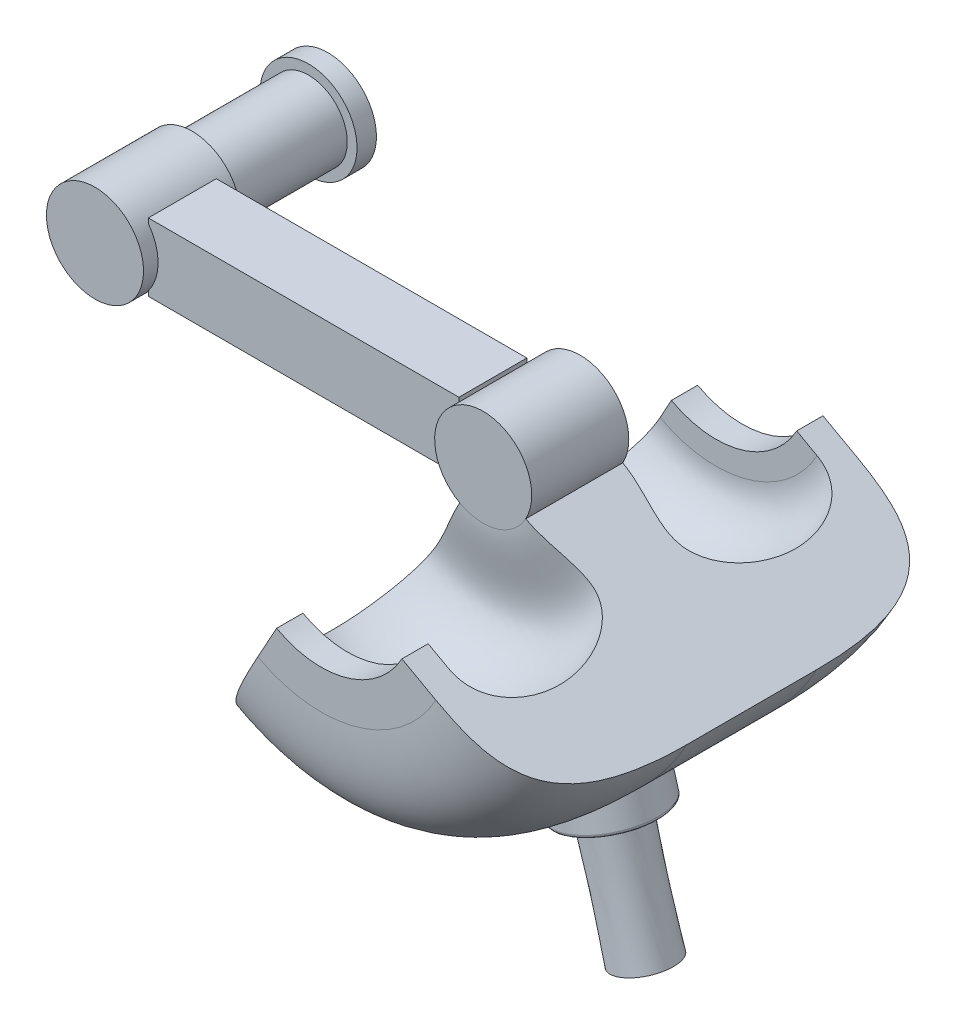
SolidWorks part; units mm, degrees
ref_plane "Front Plane" through (0, 0, 0) normal (0, 0, 1) x (1, 0, 0)
ref_plane "Top Plane" through (0, 0, 0) normal (0, 1, 0) x (1, 0, 0)
ref_plane "Right Plane" through (0, 0, 0) normal (1, 0, 0) x (0, 0, -1)
sketch "Sketch1" plane through (0, 0, 0) normal (0, 0, 1) x (1, 0, 0)
  line L0 (100, 0) -> (-100, 0)
  line L1 (-100, 0) -> (-84.615, -53.2945) construction
  line L2 (-84.615, -53.2945) -> (100, 0) construction
  line L3 (-84.615, -53.2945) -> (-100, 0) construction
  line L4 (-100, 0) -> (-148.4737, 167.9155) construction
  line L5 (-100, 0) -> (-115.2545, 52.8422)
  line L6 (-100, 0) -> (84.615, 53.2945) construction
  line L7 (84.615, 53.2945) -> (100, 0) construction
  line L8 (84.615, 53.2945) -> (100, 0) construction
  line L9 (100, 0) -> (139.1778, -135.7138) construction
  line L10 (100, 0) -> (115.2545, -52.8422)
  circle A0 centre (-100, 0) radius 25
  circle A1 centre (100, 0) radius 25
  point P4 (0, 0)
  dimension "D2" = 16.102
  dimension "D1" = 200
  dimension "D3" = 55
  dimension "D4" = 16.102
  dimension "D5" = 55
sketch "Sketch2" plane through (0, 0, 0) normal (0, 1, 0) x (1, 0, 0)
  line L0 (-100, -30.0778) -> (-100, 0) construction
  line L1 (-120, 0) -> (-111.4048, -6.7332)
  line L2 (-120, 0) -> (-100, 0)
  line L3 (-105, -30.0778) -> (-105, -15.0778)
  line L4 (-100, 0) -> (-100, -30.0778)
  line L5 (-100, -30.0778) -> (-105, -30.0778)
  line L6 (-125, 0) -> (-75, 0) construction
  line L9 (-125, -5) -> (-125, -7.9927) construction
  line L10 (-125, -5) -> (-125, -15.0778)
  line L11 (-115, -15.0778) -> (-125, -15.0778)
  line L12 (-125, -5) -> (-125, 0)
  line L13 (-125, 0) -> (-120, 0)
  line L14 (-113.6173, -5) -> (-113.6173, -15.0778)
  line L15 (-113.6173, -15.0778) -> (-115, -15.0778)
  line L16 (-113.6173, -15.0778) -> (-105, -15.0778)
  spline S0 degree 3 poles (-111.4048, -6.7332) (-109.6654, -8.0958) (-107.132, -10.6266) (-105, -13.4894) (-105, -15.0778) knots 0 0 0 0 0.616179 1 1 1 1
  dimension "D1" = 5
  dimension "D2" = 20
  dimension "D3" = 10.9185
  dimension "D4" = 15
  dimension "D5" = 5
  dimension "D6" = 5
  dimension "D7" = 5
  dimension "D8" = 10
  dimension "D9" = 15
  dimension "D10" = 15.0778
sketch "Sketch3" plane through (0, 0, 0) normal (0, 1, 0) x (1, 0, 0)
  line L5 (-125, -7.5389) -> (-80.1507, -7.5389) construction
  line L8 (-120, 0) -> (-100, 0) construction
  line L9 (-125, -32.5389) -> (-125, 17.4611)
  line L10 (-100, 0) -> (-100, 17.4611)
  line L11 (-100, 17.4611) -> (-125, 17.4611)
  line L12 (-100, 0) -> (-100, -15.0778)
  line L13 (-100, 0) -> (-100, -30.0778) construction
  line L14 (-100, -15.0778) -> (-100, -32.5389)
  line L15 (-100, -32.5389) -> (-125, -32.5389)
  point P10 (-100, -7.5389)
  dimension "D1" = 7.5389
  dimension "D2" = 25
revolve "Revolve2" add sketch "Sketch3" angle 360 about L4
sketch "Sketch4" plane through (0, 0, 0) normal (0, 0, 1) x (1, 0, 0)
  circle A0 centre (100, 0) radius 25
ref_plane "Plane1" through (80, 0, 0) normal (1, 0, 0) x (0, 0, -1)
ref_plane "Plane2" through (-80, 0, 0) normal (1, 0, 0) x (0, 0, -1)
sketch "Sketch5" plane through (80, 0, 0) normal (1, 0, 0) x (0, 0, -1)
  line L11 (9.9611, -17.5) -> (-25.0389, -17.5)
  line L12 (9.9611, -17.5) -> (9.9611, 17.5)
  line L13 (9.9611, 17.5) -> (-25.0389, 17.5)
  line L14 (-25.0389, -17.5) -> (-25.0389, 17.5)
  point P12 (-7.5389, 0)
  dimension "D1" = 35
  dimension "D2" = 35
sketch "Sketch6" plane through (-80, 0, 0) normal (1, 0, 0) x (0, 0, -1)
  line L12 (9.9611, -17.5) -> (-25.0389, -17.5)
  line L13 (9.9611, -17.5) -> (9.9611, 17.5)
  line L14 (9.9611, 17.5) -> (-25.0389, 17.5)
  line L15 (-25.0389, -17.5) -> (-25.0389, 17.5)
  point P6 (-7.5389, 0)
  dimension "D1" = 35
  dimension "D2" = 35
sketch "Sketch7" plane through (0, 0, 0) normal (1, 0, 0) x (0, 0, -1)
  line L0 (-7.5389, 45) -> (-7.5389, -15)
  point P3 (-7.5389, 15)
ref_plane "Plane3" through (0, 0, 7.5389) normal (0, 0, 1) x (1, 0, 0)
loft "Loft2" add profiles "Sketch6", "Sketch5" connector at (-80, -17.5, -9.9611) connector at (80, -17.5, -9.9611)
sketch "Sketch10" plane through (0, 0, 7.5389) normal (0, 0, 1) x (1, 0, 0)
  circle A0 centre (100, 0) radius 25
extrude "Boss-Extrude2" add sketch "Sketch10" along normal mid plane 50
sketch "Sketch11" plane through (0, 0, 7.5389) normal (0, 0, 1) x (1, 0, 0)
  line L0 (100, 0) -> (115.2545, -52.8422) construction
ref_plane "Plane4" through (7.6925, -26.6473, 0) normal (0.2774, -0.9608, 0) x (-0.9608, -0.2774, 0)
ref_plane "Plane5" through (92.3075, 26.6473, 0) normal (0.9608, 0.2774, 0) x (0, 0, -1)
sketch "Sketch12" plane through (92.3075, 26.6473, 0) normal (0.9608, 0.2774, 0) x (0, 0, -1)
  line L0 (-32.5389, -75.009) -> (17.4611, -75.009) construction
  line L1 (-32.5389, -2.7354) -> (-32.5389, -52.7354) construction
  line L2 (17.4611, -52.7354) -> (17.4611, -2.7354) construction
  line L3 (-7.5389, -84.4009) -> (-7.5389, -65.617)
  line L4 (-22.5389, -65.617) -> (-47.5389, -65.617)
  line L5 (-47.5389, -65.617) -> (-47.5389, -78.1293)
  line L6 (-7.5389, -65.617) -> (-7.5389, -132.7956) construction
  line L7 (-22.5389, -65.617) -> (-22.5389, -52.7354)
  line L8 (-32.5389, -52.7354) -> (17.4611, -52.7354) construction
  line L9 (-127.5389, -120.3474) -> (-132.5389, -120.3474)
  line L10 (-132.5389, -120.3474) -> (-132.5389, -150.3474)
  line L11 (-132.5389, -150.3474) -> (-112.5389, -150.3474)
  line L12 (-112.5389, -150.3474) -> (-112.5389, -128.4544)
  line L13 (-47.5389, -108.1293) -> (32.4611, -108.1293)
  line L14 (-90.9173, -108.1293) -> (-47.5389, -108.1293)
  line L15 (117.4611, -120.3474) -> (117.4611, -150.3474)
  line L16 (117.4611, -150.3474) -> (97.4611, -150.3474)
  line L17 (97.4611, -150.3474) -> (97.4611, -128.4544)
  line L18 (75.8395, -108.1293) -> (32.4611, -108.1293)
  line L19 (32.4611, -65.617) -> (32.4611, -78.1293)
  line L20 (7.4611, -65.617) -> (32.4611, -65.617)
  line L21 (7.4611, -65.617) -> (7.4611, -52.7354)
  line L22 (112.4611, -120.3474) -> (117.4611, -120.3474)
  line L23 (-112.5389, -139.4009) -> (-7.5389, -139.4009) construction
  line L24 (-32.5389, -27.7354) -> (-61.8307, -27.7354) construction
  spline S0 degree 3 poles (-47.5389, -78.1293) (-56.791, -78.1293) (-92.4711, -91.2818) (-119.9145, -99.872) (-127.5389, -120.3474) knots 0 0 0 0 0.409199 1 1 1 1
  spline S1 degree 2 poles (-112.5389, -128.4544) (-109.5542, -110.7568) (-90.9173, -108.1293) knots 0 0 0 1 1 1
  spline S2 degree 2 poles (97.4611, -128.4544) (94.4764, -110.7568) (75.8395, -108.1293) knots 0 0 0 1 1 1
  spline S3 degree 3 poles (32.4611, -78.1293) (41.7132, -78.1293) (77.3933, -91.2818) (104.8367, -99.872) (112.4611, -120.3474) knots 0 0 0 0 0.409199 1 1 1 1
  point P9 (-7.5389, -75.009)
  point P30 (-7.5389, -108.1293)
  dimension "D1" = 120
  dimension "D2" = 40
  dimension "D3" = 15
  dimension "D4" = 15
  dimension "D5" = 20
  dimension "D6" = 30
  dimension "D7" = 15
  dimension "D8" = 20
  dimension "D9" = 30
  dimension "D10" = 55
  dimension "D11" = 111.6655
sketch "Sketch13" plane through (92.3075, 26.6473, 0) normal (0.9608, 0.2774, 0) x (0, 0, -1)
  line L0 (-7.5389, -52.7354) -> (-7.5389, -82.7354) construction
  line L1 (-32.5389, -52.7354) -> (17.4611, -52.7354) construction
  line L2 (-32.5389, -27.7354) -> (-7.5389, -27.7354) construction
  line L3 (-32.5389, -2.7354) -> (-32.5389, -52.7354) construction
  line L4 (-7.5389, -27.7354) -> (-7.5389, -52.7354) construction
  line L5 (-7.5389, -82.7354) -> (-107.5389, -82.7354) construction
  line L6 (-41.0034, -157.4201) -> (25.9256, -157.4201)
  line L8 (-102.4645, -87.2354) -> (-102.4645, -75.2354)
  line L9 (-102.4645, -75.2354) -> (-115.9963, -75.2354)
  line L10 (-115.9963, -95.2354) -> (-115.9963, -75.2354)
  line L11 (-102.4645, -87.2354) -> (-115.9963, -75.2354) construction
  line L12 (-102.4645, -75.2354) -> (-115.9963, -95.2354) construction
  line L13 (-32.5389, -52.7354) -> (17.4611, -52.7354)
  line L14 (100.9185, -95.2354) -> (100.9185, -75.2354)
  line L15 (87.3867, -75.2354) -> (100.9185, -75.2354)
  line L16 (87.3867, -87.2354) -> (87.3867, -75.2354)
  line L17 (-7.5389, -27.7354) -> (-7.5389, 682.2646) construction
  line L18 (-7.5389, 682.2646) -> (-163.5255, 682.2646) construction
  spline S0 degree 3 poles (-32.5389, -52.7354) (-32.5389, -66.8651) (-17.6807, -96.9933) (-69.7739, -123.2553) (-102.4645, -103.261) (-102.4645, -87.2354) knots 0 0 0 0 0.304905 0.682398 1 1 1 1
  spline S1 degree 3 poles (-115.9963, -95.2354) (-115.9963, -103.8192) (-114.0214, -138.7604) (-92.6443, -157.4201) (-41.0034, -157.4201) knots 0 0 0 0 0.21752 1 1 1 1
  spline S2 degree 3 poles (100.9185, -95.2354) (100.9185, -103.8192) (98.9436, -138.7604) (77.5665, -157.4201) (25.9256, -157.4201) knots 0 0 0 0 0.21752 1 1 1 1
  spline S3 degree 3 poles (17.4611, -52.7354) (17.4611, -66.8651) (2.6029, -96.9933) (54.6961, -123.2553) (87.3867, -103.261) (87.3867, -87.2354) knots 0 0 0 0 0.304905 0.682398 1 1 1 1
  point P20 (-7.5389, -157.4201)
  dimension "D1" = 55
  dimension "D2" = 100
  dimension "D3" = 20
  dimension "D4" = 710
sketch "Sketch14" plane through (92.3075, 26.6473, 0) normal (0.9608, 0.2774, 0) x (0, 0, -1)
  line L0 (-7.5389, -27.7354) -> (-7.5389, 682.2646) construction
  dimension "D1" = 710
sketch "Sketch15" plane through (92.3075, 26.6473, 0) normal (0.9608, 0.2774, 0) x (0, 0, -1)
  line L0 (201.0989, 682.2646) -> (-216.1768, 682.2646)
  point P4 (-7.5389, 682.2646)
ref_plane "Plane6" through (82.6998, 23.8737, 0) normal (0.9608, 0.2774, 0) x (0, 0, -1)
revolve "Revolve3" add sketch "Sketch13" angle 90 mid plane about L2
sketch "Sketch16" plane through (0, 0, 7.5389) normal (0, 0, 1) x (1, 0, 0)
  line L0 (87.9188, -21.8871) -> (101.0838, -67.4913)
  line L3 (100, 0) -> (115.2545, -52.8422) construction
  line L4 (87.9188, -21.8871) -> (67.3808, -59.0952)
  arc A0 (67.3808, -59.0952) -> (159.0952, -32.6192) centre (100, 0) ccw construction
  arc A4 (67.3808, -59.0952) -> (101.0838, -67.4913) centre (100, 0) ccw
sketch "Sketch18" plane through (0, 0, 7.5389) normal (0, 0, 1) x (1, 0, 0)
  line L0 (84.615, 53.2945) -> (139.1778, -135.7138) construction
  line L1 (139.1778, -135.7138) -> (158.5925, -202.9675) construction
  dimension "D1" = 70
ref_plane "Plane7" through (35.4279, -122.724, 0) normal (0.2774, -0.9608, 0) x (-0.9608, -0.2774, 0)
sketch "Sketch19" plane through (35.4279, -122.724, 0) normal (0.2774, -0.9608, 0) x (-0.9608, -0.2774, 0)
  circle A0 centre (-96.0768, -7.5389) radius 25
  point P3 (-96.0768, -7.5389)
  point P8 (-96.0768, -81.7676)
extrude "Boss-Extrude3" add sketch "Sketch19" along normal blind 50
ref_plane "Plane8" through (66.285, -229.6148, 0) normal (0.2774, -0.9608, 0) x (-0.9608, -0.2774, 0)
sketch "Sketch20" plane through (66.285, -229.6148, 0) normal (0.2774, -0.9608, 0) x (-0.9608, -0.2774, 0)
  line L0 (-187.7777, -7.5389) -> (-89.9025, -7.5389) construction
  line L1 (-187.7777, -41.0034) -> (-187.7777, 25.9256) construction
  line L2 (-96.0768, 100.9185) -> (-96.0768, -7.5389) construction
  line L3 (-48.3471, 100.9185) -> (-143.8065, 100.9185) construction
  circle A0 centre (-96.0768, -7.5389) radius 15
sketch "Sketch21" plane through (92.3075, 26.6473, 0) normal (0.9608, 0.2774, 0) x (0, 0, -1)
  line L0 (-22.5389, -177.7354) -> (-22.5389, -238.9909)
  line L1 (-7.5389, -168.9909) -> (-7.5389, -238.9909) construction
  line L10 (-22.5389, -238.9909) -> (7.4611, -238.9909) construction
  line L11 (-7.5389, -238.9909) -> (-7.5389, -168.9909) construction
  line L12 (-7.5389, 27.7354) -> (-7.5389, -168.9909) construction
  line L13 (7.4611, -177.7354) -> (7.4611, -238.9909)
  dimension "D1" = 15
sketch "Sketch22" plane through (49.2956, -170.7624, 0) normal (0.2774, -0.9608, 0) x (0.9608, 0.2774, 0)
  circle A0 centre (96.0768, 7.5389) radius 15
loft "Loft4" add profiles "Sketch22", "Sketch20" connector at (127.883, -148.0759, 12.1293) connector at (148.9404, -205.7539, 18.6777)
fillet "Fillet6" radius 1.5 2 edges at (156.0146, -139.9549, 7.5389) (165.6223, -137.1813, 7.5389)
sketch "Sketch25" plane through (0, 0, -17.4611) normal (0, 0, -1) x (-1, 0, 0)
  circle A0 centre (100, 0) radius 20
extrude "Boss-Extrude4" add sketch "Sketch25" along normal blind 60
sketch "Sketch26" plane through (0, 0, -77.4611) normal (0, 0, -1) x (-1, 0, 0)
  circle A0 centre (100, 0) radius 25
extrude "Boss-Extrude5" add sketch "Sketch26" along normal blind 10
